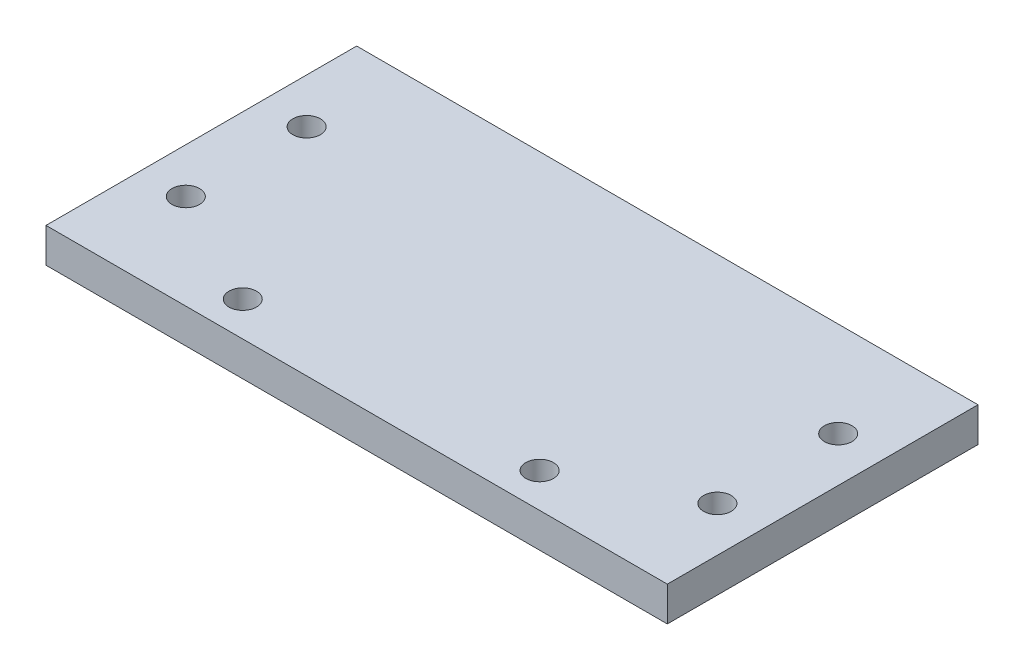
SolidWorks part; units mm, degrees
ref_plane "Front Plane" through (0, 0, 0) normal (0, 0, 1) x (1, 0, 0)
ref_plane "Top Plane" through (0, 0, 0) normal (0, 1, 0) x (1, 0, 0)
ref_plane "Right Plane" through (0, 0, 0) normal (1, 0, 0) x (0, 0, -1)
sketch "Sketch1" plane through (0, 0, 0) normal (0, 1, 0) x (1, 0, 0)
  line L0 (0, 0) -> (0, 32.9687) construction
  line L1 (-90, -45) -> (90, -45)
  line L2 (-90, -45) -> (-90, 45)
  line L3 (-90, 45) -> (90, 45)
  line L4 (90, -45) -> (90, 45)
  line L5 (-90, -45) -> (90, 45) construction
  line L6 (-90, 45) -> (90, -45) construction
  line L7 (0, 32.9687) -> (0, 0) construction
  line L8 (0, 0) -> (-70.522, 0) construction
  line L9 (5.5376, -35) -> (-43, -35) construction
  line L10 (-43, -35) -> (49.1996, -35) construction
  circle A0 centre (-77, 17.5) radius 4
  circle A1 centre (-77, -17.5) radius 4
  circle A2 centre (-43, -35) radius 4
  circle A3 centre (77, 17.5) radius 4
  circle A4 centre (77, -17.5) radius 4
  circle A5 centre (43, -35) radius 4
  point P0 (0, 0)
  dimension "D3" = 35
  dimension "D4" = 8
  dimension "D1" = 90
  dimension "D2" = 180
  dimension "D5" = 13
  dimension "D6" = 47
  dimension "D7" = 10
extrude "Boss-Extrude1" add sketch "Sketch1" along normal blind 10
